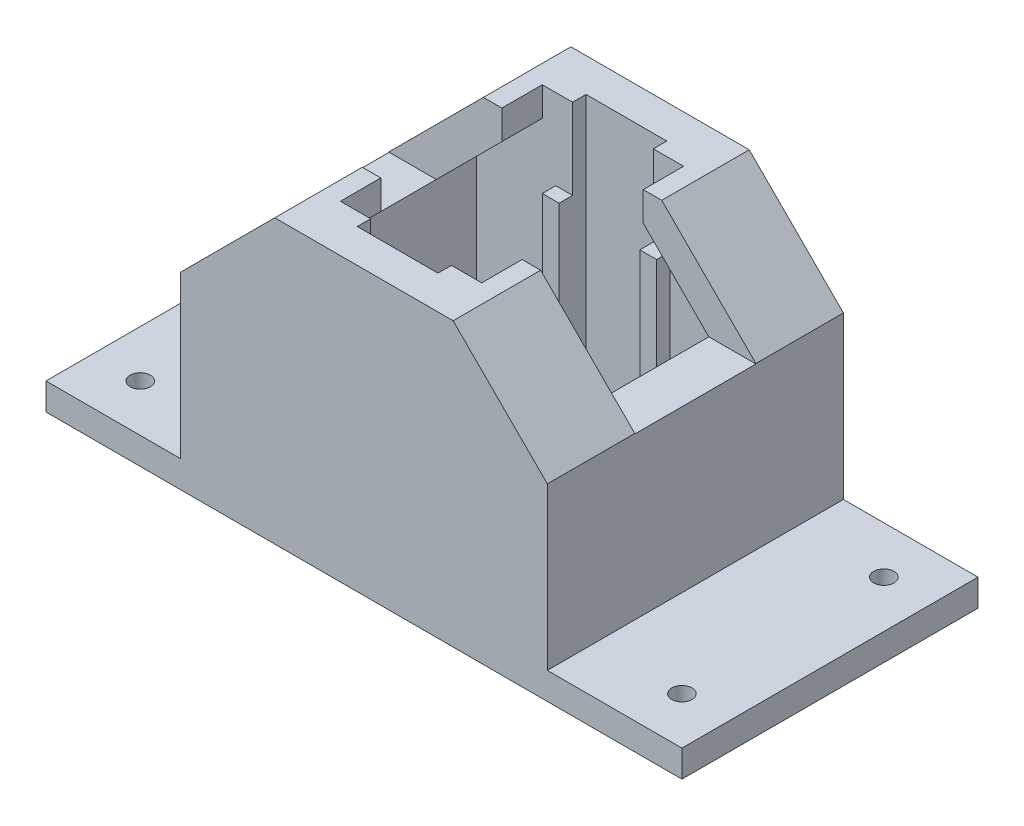
SolidWorks part; units mm, degrees
ref_plane "Płaszczyzna przednia" through (0, 0, 0) normal (0, 0, 1) x (1, 0, 0)
ref_plane "Płaszczyzna górna" through (0, 0, 0) normal (0, 1, 0) x (1, 0, 0)
ref_plane "Płaszczyzna prawa" through (0, 0, 0) normal (1, 0, 0) x (0, 0, -1)
sketch "Sketch1" plane through (0, 0, 0) normal (0, 1, 0) x (1, 0, 0)
  line L0 (0, 19.4294) -> (0, -20.6549) construction
  line L1 (-20.25, 15) -> (20.25, 15)
  line L2 (-20.25, 15) -> (-20.25, -15)
  line L3 (-20.25, -15) -> (20.25, -15)
  line L4 (20.25, 15) -> (20.25, -15)
  line L5 (-20.25, 15) -> (20.25, -15) construction
  line L6 (-20.25, -15) -> (20.25, 15) construction
  line L7 (-32.8665, 0) -> (32.8665, 0) construction
  line L8 (8.5, 13) -> (6, 13)
  line L9 (-8.5, 15) -> (-6, 15)
  line L10 (-8.5, 15) -> (-8.5, 13)
  line L11 (-8.5, 13) -> (-6, 13)
  line L12 (-6, 15) -> (-6, 13)
  line L13 (6, 15) -> (6, 13)
  line L14 (8.5, 15) -> (6, 15)
  line L15 (8.5, 15) -> (8.5, 13)
  line L16 (8.5, -15) -> (8.5, -13)
  line L17 (8.5, -15) -> (6, -15)
  line L18 (6, -15) -> (6, -13)
  line L19 (8.5, -13) -> (6, -13)
  line L20 (-8.5, -13) -> (-6, -13)
  line L21 (-6, -15) -> (-6, -13)
  line L22 (-8.5, -15) -> (-6, -15)
  line L23 (-8.5, -15) -> (-8.5, -13)
  line L24 (-27.25, 22) -> (-27.25, -22)
  line L25 (-27.25, -22) -> (27.25, -22)
  line L26 (27.25, 22) -> (27.25, -22)
  line L27 (-27.25, 22) -> (27.25, 22)
  point P0 (0, 0)
  point P10 (0, 15)
  dimension "D1" = 30
  dimension "D2" = 40.5
  dimension "D3" = 2.5
  dimension "D4" = 2
  dimension "D5" = 6
  dimension "1" = 7
extrude "Boss-Extrude1" add sketch "Sketch1" along normal blind 42 contours L15 L1 L13 L8 | L27 L24 L25 L26 L22 L23 L3 L2 L1 L4 L21 | L11 L12 L9 L10 | L20 L21 L22 L23 | L19 L18 L17 L16 region at (7.25, 0, -14) region at (0, 0, -21.2996)
chamfer "Chamfer2" distance 14 angle 45 2 edges at (27.25, 42, 0) (-27.25, 42, 0)
chamfer "Chamfer3" distance 10 angle 45 2 edges at (20.25, 35, 0) (-20.25, 35, 0) first distance on face at (18.5, 36.75, 0) first distance on face at (-18.5, 36.75, 0)
sketch "Sketch2" plane through (0, 0, -15) normal (0, 0, 1) x (1, 0, 0)
  line L1 (-27.25, 20.9289) -> (-6.1789, 42)
  line L3 (-27.25, 28) -> (-27.25, 27.9289) construction
  line L8 (0, 51.2829) -> (0, -13.1032) construction
  line L9 (-6, 42) -> (6, 42) construction
  line L12 (-27.25, 28) -> (-13.25, 42)
  line L13 (-13.25, 42) -> (-6.1789, 42)
  line L14 (-13.25, 42) -> (-27.25, 28) construction
  line L15 (-27.25, 28) -> (-27.25, 20.9289)
  line L16 (13.25, 42) -> (6.1789, 42)
  line L17 (27.25, 28) -> (13.25, 42)
  line L18 (27.25, 28) -> (27.25, 20.9289)
  line L19 (27.25, 20.9289) -> (6.1789, 42)
  dimension "D1" = 5
extrude "Boss-Extrude2" add sketch "Sketch2" along normal blind 6
ref_plane "Plane1" through (0, 0, 0) normal (0, 0, 1) x (1, 0, 0)
mirror "Mirror2" about plane through (0, 0, 0) normal (0, 0, 1) of "Boss-Extrude2"
sketch "Sketch4" plane through (0, 0, 0) normal (0, -1, 0) x (1, 0, 0)
  line L0 (0, 30.4744) -> (0, -31.4814) construction
  line L1 (27.25, 22) -> (47.25, 22)
  line L2 (27.25, 22) -> (27.25, -22)
  line L3 (27.25, -22) -> (47.25, -22)
  line L4 (47.25, 22) -> (47.25, -22)
  line L5 (-27.25, -22) -> (-47.25, -22)
  line L6 (-47.25, 22) -> (-47.25, -22)
  line L7 (-27.25, 22) -> (-47.25, 22)
  line L8 (-27.25, 22) -> (-27.25, -22)
  line L9 (-55.8577, 0) -> (55.4548, 0) construction
  circle A0 centre (40.25, 15) radius 1.5
  circle A1 centre (40.25, -15) radius 1.5
  circle A2 centre (-40.25, -15) radius 1.5
  circle A3 centre (-40.25, 15) radius 1.5
  dimension "D2" = 3
  dimension "D1" = 20
  dimension "D3" = 7
  dimension "D4" = 7
extrude "Boss-Extrude3" add sketch "Sketch4" against normal blind 4
sketch "Sketch5" plane through (0, 42, 0) normal (0, 1, 0) x (1, 0, 0)
  line L0 (0, 26.9268) -> (0, -15) construction
  line L1 (-10.5, 15) -> (10.5, 15)
  line L2 (-10.5, 15) -> (-10.5, -15)
  line L3 (-10.5, -15) -> (10.5, -15)
  line L4 (10.5, 15) -> (10.5, -15)
  line L7 (20.25, -15) -> (8.5, -15) construction
  line L8 (-6, 15) -> (6, 15) construction
  dimension "D1" = 21
extrude "Cut-Extrude1" cut sketch "Sketch5" against normal blind 12
sketch "Sketch6" plane through (0, 0, 15) normal (0, 0, -1) x (-1, 0, 0)
  line L0 (10.5, 42) -> (-10.5, 42) construction
  line L1 (-6, 42) -> (6, 42)
  line L2 (-6, 42) -> (-6, 0)
  line L3 (-6, 0) -> (6, 0)
  line L4 (6, 42) -> (6, 0)
extrude "Cut-Extrude2" cut sketch "Sketch6" against normal blind 2
mirror "Mirror3" about plane through (0, 0, 0) normal (0, 0, 1) of "Cut-Extrude2"
